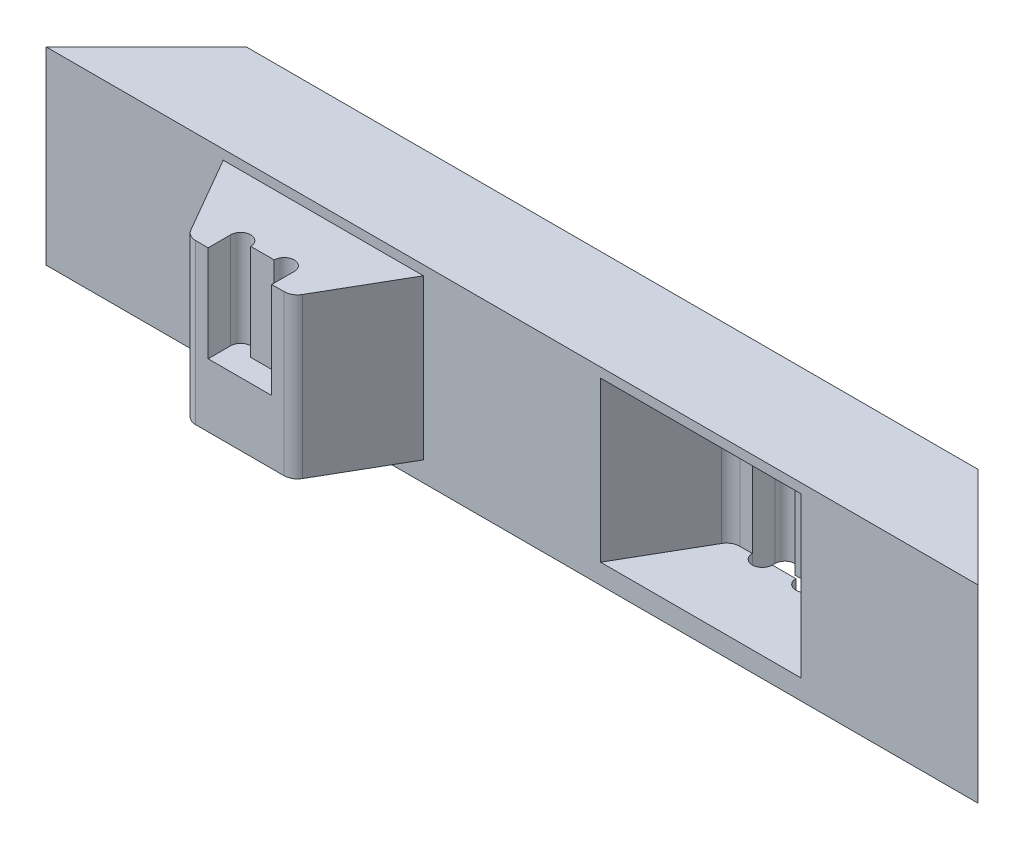
SolidWorks part; units mm, degrees
material "Macor"
ref_plane "Front Plane" through (0, 0, 0) normal (0, 0, 1) x (1, 0, 0)
ref_plane "Top Plane" through (0, 0, 0) normal (0, 1, 0) x (1, 0, 0)
ref_plane "Right Plane" through (0, 0, 0) normal (1, 0, 0) x (0, 0, -1)
sketch "Sketch1" plane through (0, 0, 0) normal (0, 1, 0) x (1, 0, 0)
  line L1 (-69.85, -10) -> (69.85, -10)
  line L2 (-69.85, -10) -> (-69.85, 10)
  line L3 (-69.85, 10) -> (69.85, 10)
  line L4 (69.85, -10) -> (69.85, 10)
  line L5 (-69.85, -10) -> (69.85, 10) construction
  line L6 (-69.85, 10) -> (69.85, -10) construction
  point P0 (0, 0)
  dimension "D1" = 139.7
  dimension "D2" = 20
extrude "Boss-Extrude1" add sketch "Sketch1" along normal mid plane 28.34
ref_plane "Plane1" through (0, -11.17, 0) normal (0, -1, 0) x (-1, 0, 0)
sketch "Sketch3" plane through (0, -11.17, 0) normal (0, -1, 0) x (-1, 0, 0)
  line L0 (-13.2833, -10) -> (-20.5002, 2.5)
  line L1 (69.85, -10) -> (-69.85, -10) construction
  line L2 (-20.5002, 2.5) -> (-36.0665, 2.5)
  line L3 (-36.0665, 2.5) -> (-43.2833, -10)
  line L4 (-43.2833, -10) -> (-13.2833, -10)
  line L5 (69.85, -10) -> (43.2833, -10) construction
  line L6 (43.2833, -10) -> (13.2833, -10) construction
  line L7 (13.2833, -10) -> (-13.2833, -10) construction
  line L8 (-43.2833, -10) -> (-69.85, -10) construction
  dimension "D1" = 12.5
  dimension "D2" = 30
  dimension "D3" = 60
extrude "Cut-Extrude1" cut sketch "Sketch3" against normal blind 23.9
sketch "Sketch4" plane through (0, -11.17, 0) normal (0, -1, 0) x (-1, 0, 0)
  line L0 (43.2833, -10) -> (13.2833, -10) construction
  line L1 (69.85, -10) -> (43.2833, -10) construction
  line L2 (43.2833, -10) -> (13.2833, -10)
  line L3 (69.85, -10) -> (43.2833, -10) construction
  line L4 (43.2833, -10) -> (36.0665, -22.5)
  line L5 (36.0665, -22.5) -> (20.5002, -22.5)
  line L6 (20.5002, -22.5) -> (13.2833, -10)
  line L7 (-13.2833, -10) -> (-20.5002, 2.5) construction
  line L8 (-20.5002, 2.5) -> (-36.0665, 2.5) construction
extrude "Boss-Extrude2" add sketch "Sketch4" against normal up to surface (23.9 mm away) up to face at (28.2833, 12.73, 3.75)
chamfer "Chamfer1" distance 20 angle 45 2 edges at (69.85, 0, -10) (-69.85, 0, -10)
chamfer "Chamfer2" distance 5 angle 45 1 edges at (0, 14.17, -10)
sketch "Sketch5" plane through (0, 12.73, 0) normal (0, 1, 0) x (1, 0, 0)
  line L5 (-33.0483, -19.12) -> (-33.0483, -22.5)
  line L6 (-36.0665, -22.5) -> (-20.5002, -22.5) construction
  line L7 (-33.0483, -22.5) -> (-23.5183, -22.5)
  line L8 (-23.5183, -22.5) -> (-23.5183, -19.12)
  line L9 (-30.0483, -19.12) -> (-26.5183, -19.12)
  arc A0 (-33.0483, -19.12) -> (-30.0483, -19.12) centre (-31.5483, -19.12) cw
  arc A1 (-23.5183, -19.12) -> (-26.5183, -19.12) centre (-25.0183, -19.12) ccw
  point P4 (-28.2833, -22.5)
  point P7 (-28.2833, -22.5)
  point P10 (0, 0)
  dimension "D3" = 1.5
  dimension "D1" = 3.38
  dimension "D2" = 9.53
extrude "Cut-Extrude2" cut sketch "Sketch5" against normal blind 14.41
sketch "Sketch7" plane through (0, -14.17, 0) normal (0, -1, 0) x (1, 0, 0)
  line L0 (20.5002, -2.5) -> (36.0665, -2.5) construction
  line L1 (20.5002, -2.5) -> (36.0665, -2.5) construction
  line L2 (23.5183, -2.5) -> (33.0483, -2.5) construction
  line L3 (-33.0483, 22.5) -> (-23.5183, 22.5) construction
  line L4 (23.5183, -2.5) -> (23.5183, -5.88)
  line L5 (33.0483, -2.5) -> (33.0483, -5.88)
  line L6 (-33.0483, 19.12) -> (-33.0483, 22.5) construction
  line L7 (26.5183, -5.88) -> (30.0483, -5.88)
  line L8 (26.5183, -2.5) -> (30.0483, -2.5)
  arc A0 (23.5183, -5.88) -> (26.5183, -5.88) centre (25.0183, -5.88) ccw
  arc A1 (33.0483, -5.88) -> (30.0483, -5.88) centre (31.5483, -5.88) cw
  arc A4 (-33.0483, 19.12) -> (-30.0483, 19.12) centre (-31.5483, 19.12) ccw construction
  arc A5 (23.5183, -2.5) -> (26.5183, -2.5) centre (25.0183, -2.5) cw
  arc A6 (33.0483, -2.5) -> (30.0483, -2.5) centre (31.5483, -2.5) ccw
  point P2 (28.2833, -2.5)
  point P5 (28.2833, -2.5)
extrude "Cut-Extrude3" cut sketch "Sketch7" against normal blind 19.02
fillet "Fillet1" radius 2 4 edges at (36.0665, 0.78, -2.5) (20.5002, 0.78, -2.5) (-20.5002, 0.78, 22.5) (-36.0665, 0.78, 22.5)
